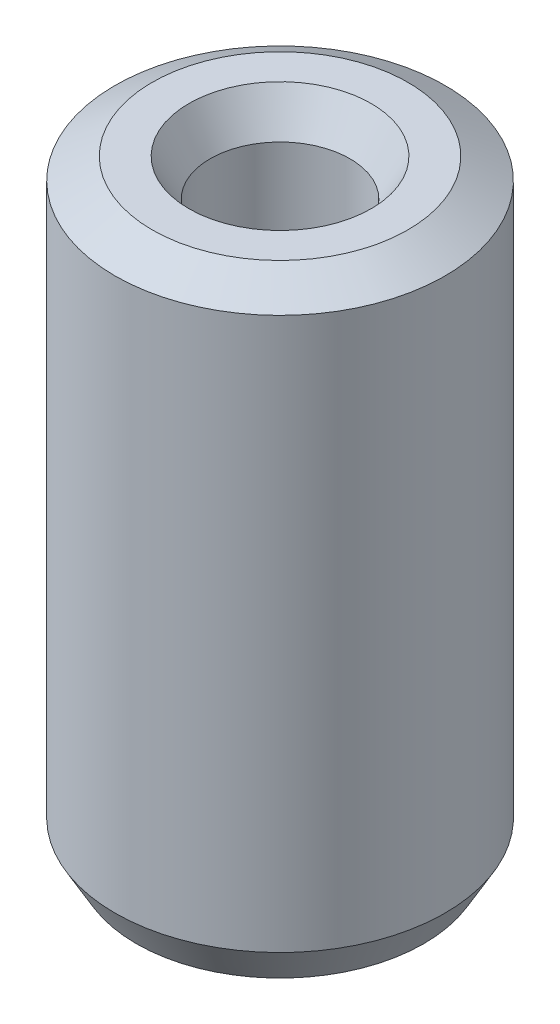
SolidWorks part; units mm, degrees
ref_plane "Front Plane" through (0, 0, 0) normal (0, 0, 1) x (1, 0, 0)
ref_plane "Top Plane" through (0, 0, 0) normal (0, 1, 0) x (1, 0, 0)
ref_plane "Right Plane" through (0, 0, 0) normal (1, 0, 0) x (0, 0, -1)
sketch "Sketch1" plane through (0, 0, 0) normal (0, 1, 0) x (1, 0, 0)
  circle A0 centre (0, 0) radius 5
  dimension "SLEEVE_OD" = 10
extrude "Boss-Extrude1" add sketch "Sketch1" along normal blind 18.4906
sketch "Sketch2" plane through (0, 0, 0) normal (0, 1, 0) x (1, 0, 0)
  circle A0 centre (0, 0) radius 2.1179
  dimension "BORE_D" = 4.2357
extrude "Cut-Extrude1" cut sketch "Sketch2" along normal through all
chamfer "Chamfer1" distance 0.6444 angle 60.225 4 edges at (0, 18.4906, 2.1179) (0, 0, 2.1179) (0, 0, 5) (0, 18.4906, 5) first distance on face at (0, 18.4906, 2.1179) first distance on face at (0, 0, 2.1179) first distance on face at (0, 18.4906, 5)
